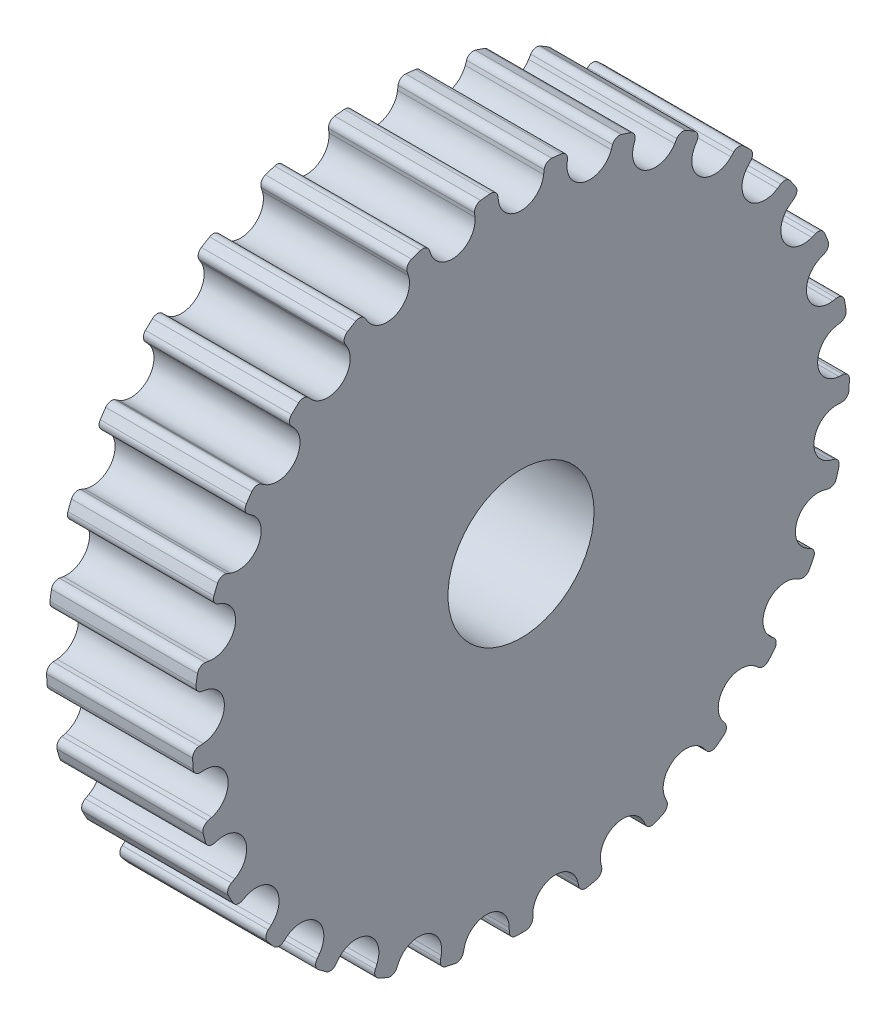
SolidWorks part; units mm, degrees
ref_plane "前视基准面" through (0, 0, 0) normal (0, 0, 1) x (1, 0, 0)
ref_plane "上视基准面" through (0, 0, 0) normal (0, 1, 0) x (1, 0, 0)
ref_plane "右视基准面" through (0, 0, 0) normal (1, 0, 0) x (0, 0, -1)
sketch "草图1" plane through (0, 0, 0) normal (0, 0, 1) x (1, 0, 0)
  line L0 (0, 0) -> (64.8368, 0) construction
  line L1 (0, 4.5006) -> (0, 9.0012)
  line L2 (0.2, 22.503) -> (122.8, 22.503)
  line L3 (123, 22.303) -> (123, 18.0024)
  line L4 (0, 9.0012) -> (44, 9.0012) construction
  line L5 (44, 10.7607) -> (44, 16.2429)
  line L6 (123, 4.5006) -> (0, 4.5006)
  line L8 (5.9947, 255.8006) -> (12.0053, 255.8006) construction
  line L11 (9, 255.8006) -> (9, 4.5006) construction
  line L12 (44, 18.0024) -> (0, 18.0024) construction
  line L13 (123, 18.0024) -> (79, 18.0024) construction
  line L14 (79, 16.2429) -> (79, 10.7607)
  line L15 (79, 9.0012) -> (123, 9.0012) construction
  line L16 (61.5, 4.5006) -> (61.5, 22.503) construction
  line L17 (123, 9.0012) -> (123, 4.5006)
  line L18 (0, 18.0024) -> (0, 22.303)
  line L19 (44, 16.2022) -> (79, 16.2022) construction
  line L20 (44, 10.8014) -> (79, 10.8014) construction
  line L21 (123, 18.0024) -> (123, 16.2022) construction
  line L22 (123, 16.2022) -> (79, 16.2022) construction
  line L23 (79, 10.8014) -> (123, 10.8014) construction
  line L24 (123, 10.8014) -> (123, 9.0012) construction
  line L25 (79, 16.2429) -> (123, 18.0024)
  line L26 (44, 16.2429) -> (0, 18.0024)
  line L27 (44, 10.7607) -> (0, 9.0012)
  line L28 (79, 10.7607) -> (123, 9.0012)
  arc A0 (0, 22.303) -> (0.2, 22.503) centre (0.2, 22.303) cw
  arc A1 (123, 22.303) -> (122.8, 22.503) centre (122.8, 22.303) ccw
  dimension "r" = 0.2
  dimension "d" = 9.0012
  dimension "S" = 35
  dimension "S2" = 1.8002
  dimension "D3" = 2.29
  dimension "d2" = 36.0048
  dimension "D4" = 2.29
  dimension "d1" = 18.0024
  dimension "L" = 123
  dimension "B" = 123
  dimension "da" = 45.006
revolve "旋转1" add sketch "草图1" angle 360 about L0
chamfer "倒角1" distance 1 angle 45 2 edges at (0, 0, 4.5006) (123, 0, 4.5006)
sketch "草图4" plane through (0, 0, 0) normal (-1, 0, 0) x (0, 0, 1)
  line L1 (-1.5, 4.2433) -> (1.5, 4.2433)
  line L2 (-1.5, 4.2433) -> (-1.5, 5.6433)
  line L3 (-1.5, 5.6433) -> (1.5, 5.6433)
  line L4 (1.5, 4.2433) -> (1.5, 5.6433)
  circle A0 centre (0, 0) radius 4.5006 construction
  dimension "键槽宽度" = 3
  dimension "t1" = 1.4
extrude "切除-拉伸1" cut sketch "草图4" against normal through all
fillet "圆角1" radius 2 4 edges at (79, 0, 16.2429) (44, 0, 10.7607) (44, 0, 16.2429) (79, 0, 10.7607)
fillet "圆角2" radius 2.5 2 edges at (123, 0, 9.0012) (0, 0, 9.0012)
ref_axis "基准轴1" through (-6.7679, 0, 0) along (1, 0, 0)
sketch "草图5" plane through (0, 0, 0) normal (1, 0, 0) x (0, 0, -1)
  line L0 (0, 255.8006) -> (0, 4.5006) construction
  circle A0 centre (0, 13.5018) radius 2.7004
  dimension "D1" = 5.4007
  dimension "D2" = 13.5018
extrude "切除-拉伸2" cut sketch "草图5" along normal through all
pattern_circular "阵列(圆周)1" count 4 over 360 about axis through (0, 0, 0) along (1, 0, 0) of "切除-拉伸2"
sketch "草图6" plane through (0, 0, 0) normal (1, 0, 0) x (0, 0, -1)
  line L0 (0, 0) -> (0, 456.5571) construction
  line L1 (-1.5818, 21.9851) -> (-1.5484, 21.7129)
  line L2 (-2.5805, 22.3546) -> (-7.0305, 58.5975)
  line L3 (1.5818, 21.9851) -> (1.5484, 21.7129)
  line L4 (2.5805, 22.3546) -> (7.0305, 58.5975)
  circle A0 centre (0, 0) radius 20.343 construction
  arc A1 (-2.1031, 22.4045) -> (-2.5805, 22.3546) centre (0, 0) ccw
  arc A2 (-2.1031, 22.4045) -> (-1.5818, 21.9851) centre (-2.0582, 21.9266) cw
  arc A3 (-1.5484, 21.7129) -> (1.5484, 21.7129) centre (0, 21.903) ccw
  arc A4 (-7.0305, 58.5975) -> (7.0305, 58.5975) centre (0, 0) cw
  arc A5 (2.1031, 22.4045) -> (1.5818, 21.9851) centre (2.0582, 21.9266) ccw
  arc A6 (2.1031, 22.4045) -> (2.5805, 22.3546) centre (0, 0) cw
  point P4 (0, 3.25)
  point P6 (0, 454.3971)
  dimension "D1" = 40.686
  dimension "D4" = 22.503
  dimension "ra" = 0.48
  dimension "rf" = 1.56
  dimension "hg" = 2.16
  dimension "D3" = 36.5151
  dimension "bw" = 3.25
  dimension "angle" = 14
  dimension "D5" = 0.48
extrude "切除-拉伸3" cut sketch "草图6" along normal up to next
pattern_circular "阵列(圆周)3" count 29 over 360 about axis through (-6.7679, 0, 0) along (1, 0, 0) of "切除-拉伸3"
ref_plane "基准面1" through (61.5, 0, 0) normal (1, 0, 0) x (0, 0, -1)
sketch "草图7" plane through (123, 0, 0) normal (1, 0, 0) x (0, 0, -1)
  circle A0 centre (0, 0) radius 28.266
  dimension "D1" = 56.532
extrude "切除-拉伸4" cut sketch "草图7" against normal blind 56.5
mirror "镜向1" about plane through (61.5, 0, 0) normal (1, 0, 0) of "切除-拉伸4"
sketch "草图8" plane through (66.5, 0, 0) normal (1, 0, 0) x (0, 0, -1)
  circle A0 centre (0, 0) radius 17.3478
  dimension "D1" = 34.6956
extrude "凸台-拉伸1" add sketch "草图8" against normal up to surface (10 mm away) up to face at (56.5, 0, 0)
sketch "草图9" plane through (66.5, 0, 0) normal (1, 0, 0) x (0, 0, -1)
  circle A0 centre (0, 0) radius 5
  dimension "D1" = 10
extrude "切除-拉伸5" cut sketch "草图9" against normal up to surface (10 mm away) up to face at (56.5, 0, 0)
equation "\"D1@草图5\" = \"d2@草图1\" / 2 - \"d1@草图1\" / 2 - \"S2@草图1\" * 2"
equation "\"D2@草图5\" = \"d1@草图1\" / 2 + \"S2@草图1\" + \"D1@草图5\" / 2"
equation "\"D1@草图6\" = \"da@草图1\" - \"hg@草图6\" - \"hg@草图6\""
equation "\"D4@草图6\" = \"da@草图1\" / 2"
equation "\"D5@草图6\" = \"ra@草图6\""
